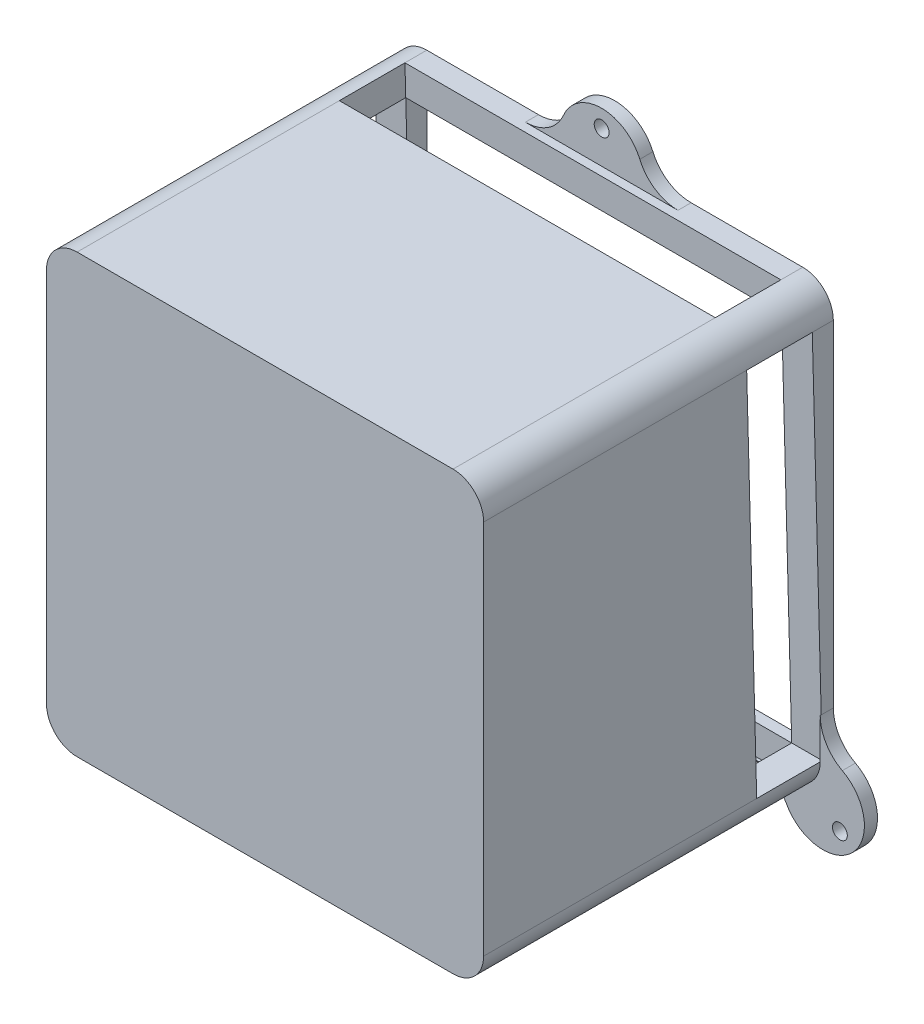
SolidWorks part; units mm, degrees
ref_plane "Plan de face" through (0, 0, 0) normal (0, 0, 1) x (1, 0, 0)
ref_plane "Plan de dessus" through (0, 0, 0) normal (0, 1, 0) x (1, 0, 0)
ref_plane "Plan de droite" through (0, 0, 0) normal (1, 0, 0) x (0, 0, -1)
sketch "Esquisse1" plane through (0, 0, 0) normal (0, 0, 1) x (1, 0, 0)
  line L1 (0, 0) -> (100, 0)
  line L2 (0, 0) -> (0, 100)
  line L3 (0, 100) -> (100, 100)
  line L4 (100, 0) -> (100, 100)
  dimension "D1" = 100
  dimension "D2" = 100
extrude "Boss.-Extru.1" add sketch "Esquisse1" along normal blind 80
sketch "Esquisse2" plane through (0, 0, 0) normal (0, 0, -1) x (-1, 0, 0)
  line L8 (-7, 7) -> (-7, 93)
  line L9 (-7, 93) -> (-93, 93)
  line L10 (-93, 93) -> (-93, 7)
  line L11 (-93, 7) -> (-7, 7)
  line L12 (-7, 7) -> (-7, 93)
  line L13 (-7, 93) -> (-93, 93)
  line L14 (-93, 93) -> (-93, 7)
  line L15 (-93, 7) -> (-7, 7)
  dimension "D1" = 7
extrude "Enlèv. mat.-Extru.1" cut sketch "Esquisse2" against normal offset from surface (70 mm away) 10 up to face at (50, 50, 80)
sketch "Esquisse3" plane through (0, 0, 80) normal (0, 0, 1) x (1, 0, 0)
  line L0 (95, 95) -> (5, 95)
  line L1 (5, 95) -> (5, 5)
  line L2 (5, 5) -> (95, 5)
  line L3 (95, 5) -> (95, 95)
  line L4 (0, 100) -> (0, 0)
  line L5 (0, 0) -> (100, 0)
  line L6 (100, 0) -> (100, 100)
  line L7 (100, 100) -> (0, 100)
  line L8 (0, 100) -> (0, 0)
  line L9 (0, 0) -> (100, 0)
  line L10 (100, 0) -> (100, 100)
  line L11 (100, 100) -> (0, 100)
  dimension "D1" = 0
  dimension "D2" = 5
extrude "Boss.-Extru.2" [suppressed] add sketch "Esquisse3" along normal blind 10
sketch "Esquisse4" plane through (0, 0, 0) normal (0, 0, -1) x (-1, 0, 0)
  line L0 (-93, 7) -> (-116.2207, -16.2207) construction
  line L1 (-7, 7) -> (8.1122, -8.1122) construction
  line L6 (0, 0) -> (-100, 0) construction
  line L7 (3.2972, -11.3596) -> (13.4788, -1.1781) construction
  line L8 (-114.7245, 0.0676) -> (-101.0769, -13.5799) construction
  line L9 (-50, 93) -> (-50, 115.4924) construction
  line L10 (-7, 93) -> (-93, 93) construction
  line L11 (-100, 100) -> (0, 100) construction
  line L12 (-62.0341, 111.5) -> (-40.7837, 111.5) construction
  line L13 (-46.9586, 93) -> (-53.0414, 93)
  circle A0 centre (-104.5, -4.5) radius 1.5
  circle A1 centre (4.5, -4.5) radius 1.5
  circle A2 centre (0.6109, -0.6109) radius 9.5
  circle A3 centre (-100.6109, -0.6109) radius 9.5
  circle A4 centre (-50, 107.5) radius 1.5
  arc A5 (-46.9586, 93) -> (-53.0414, 93) centre (-50, 102) ccw
  point P28 (-50, 100)
  dimension "D1" = 3
  dimension "D4" = 3
  dimension "D7" = 19
  dimension "D8" = 19
  dimension "D10" = 3
  dimension "D12" = 19
  dimension "D2" = 4.5
  dimension "D3" = 4
  dimension "D5" = 4.5
  dimension "D6" = 4
  dimension "D9" = 7.5
  dimension "D11" = 4
extrude "Boss.-Extru.3" add sketch "Esquisse4" against normal blind 3
fillet "Congé1" radius 7 4 edges at (100, 0, 41.5) (0, 100, 40) (0, 0, 41.5) (100, 100, 40)
fillet "Congé3" [suppressed] radius 1 type face fillet
fillet "Congé4" radius 9.5 6 edges at (8.8694, 0, 1.5) (0, 8.8694, 1.5) (91.1306, 0, 1.5) (100, 8.8694, 1.5) (59.2871, 100, 1.5) (40.7129, 100, 1.5)
hole_wizard "Dégagement M31" positions "Esquisse5" profile "Esquisse6" hole size "M3" standard "ISO" end condition up to next
sketch "Esquisse5" plane through (0, 0, 3) normal (0, 0, 1) x (1, 0, 0)
  point P0 (104.5, -4.5)
  point P3 (-4.5, -4.5)
  point P6 (50, 107.5)
sketch "Esquisse6" plane through (104.5, -4.5, 3) normal (1, 0, 0) x (0, -1, 0)
  line L0 (0, 0) -> (0, 3)
  line L1 (0, 3) -> (1.7, 3)
  line L2 (1.7, 3) -> (1.7, 0)
  line L5 (1.7, 0) -> (0, 0)
  line L11 (0, -6.35) -> (0, 107.95) construction
  dimension "Diamètre du perçage jusqu'au prochain" = 3.4
  dimension "Profondeur du perçage jusqu'au prochain" = 3
ref_plane "Plan1" through (0, 100, 0) normal (0, 1, 0) x (1, 0, 0)
ref_plane "Plan2" through (0, 102.0609, 2.7218) normal (0, 0.9996, 0.0267) x (1, 0, 0)
sketch "Esquisse8" plane through (0, 102.0609, 2.7218) normal (0, 0.9996, 0.0267) x (1, 0, 0)
  line L0 (7, 2.6658) -> (7, -77.3057) construction
  line L1 (7, -17.3342) -> (93, -17.3342)
  line L2 (7, -17.3342) -> (7, -2.3342)
  line L3 (7, -2.3342) -> (93, -2.3342)
  line L4 (93, -17.3342) -> (93, -2.3342)
  line L5 (93, -77.3057) -> (93, 2.6658) construction
  line L6 (0, 2.6658) -> (100, 2.6658) construction
  dimension "D1" = 15
  dimension "D2" = 5
extrude "Enlèv. mat.-Extru.2" cut sketch "Esquisse8" against normal up to surface (101.6349 mm away) up to face at (50, 0, 21.5)
sketch "Esquisse9" plane through (93, 0, 0) normal (-1, 0, 0) x (0, 0, 1)
  line L0 (19.8204, 93) -> (17.527, 7)
  line L1 (17.527, 7) -> (2.5217, 7)
  line L2 (2.5217, 7) -> (4.8151, 93)
  line L3 (4.8151, 93) -> (19.8204, 93)
extrude "Enlèv. mat.-Extru.3" cut sketch "Esquisse9" along normal up to surface (93 mm away) from surface up to face at (0, 38.7272, 27.6667) starting at face at (100, 38.7272, 27.6667)
